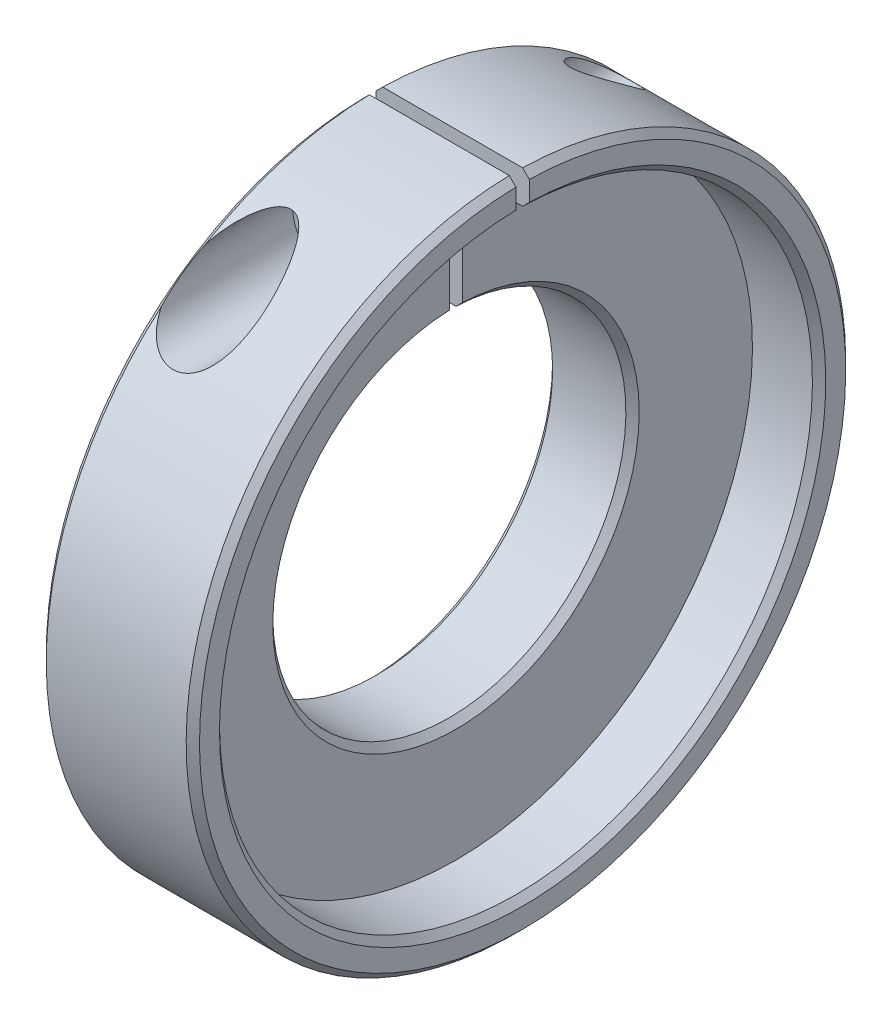
SolidWorks part; units mm, degrees
material "1.8901 (S460N)"
ref_plane "Plan de face" through (0, 0, 0) normal (0, 0, 1) x (1, 0, 0)
ref_plane "Plan de dessus" through (0, 0, 0) normal (0, 1, 0) x (1, 0, 0)
ref_plane "Plan de droite" through (0, 0, 0) normal (1, 0, 0) x (0, 0, -1)
sketch "Esquisse1" plane through (0, 0, 0) normal (0, 0, 1) x (1, 0, 0)
  line L0 (0, 0) -> (-25.4685, 0) construction
  line L1 (0, 13.25) -> (-6.5, 13.25)
  line L2 (-6.5, 13.25) -> (-6.5, 24.75)
  line L3 (-6.5, 24.75) -> (5, 24.75)
  line L4 (5, 24.75) -> (5, 22.25)
  line L5 (5, 22.25) -> (0, 22.25)
  line L6 (0, 22.25) -> (0, 13.25)
  dimension "D1" = 26.5
  dimension "D2" = 11.5
  dimension "D3" = 5
  dimension "D4" = 44.5
  dimension "D5" = 49.5
revolve "Révolution1" add sketch "Esquisse1" angle 360 about L0
sketch "Esquisse2" plane through (5, 0, 0) normal (1, 0, 0) x (0, 0, -1)
  line L1 (0.5, 0) -> (-0.5, 0)
  line L2 (0.5, 0) -> (0.5, 24.75)
  line L3 (0.5, 24.75) -> (-0.5, 24.75)
  line L4 (-0.5, 0) -> (-0.5, 24.75)
  circle A0 centre (0, 0) radius 24.75 construction
  dimension "D1" = 1
extrude "Enlèv. mat.-Extru.1" cut sketch "Esquisse2" against normal through all
sketch "Esquisse3" plane through (0, 0, 0) normal (0, 0, 1) x (1, 0, 0)
  line L0 (-3.25, 13.2406) -> (-3.25, 20) construction
  line L1 (0, 13.2406) -> (-6.5, 13.2406) construction
  circle A0 centre (-3.25, 20) radius 1.75
  dimension "D1" = 3.5
  dimension "D2" = 20
extrude "Enlèv. mat.-Extru.2" cut sketch "Esquisse3" against normal through all and the other way through all
ref_plane "Plan1" through (-3.25, 0, 0) normal (-1, 0, 0) x (0, 0, 1)
sketch "Esquisse4" plane through (-3.25, 0, 0) normal (-1, 0, 0) x (0, 0, 1)
  line L0 (6, 18.25) -> (6, 21.75) construction
  line L1 (6, 17) -> (17.9878, 17)
  line L2 (6, 17) -> (6, 20)
  line L3 (6, 20) -> (17.9878, 20)
  line L4 (17.9878, 17) -> (17.9878, 20)
  line L5 (0.5, 18.25) -> (16.7183, 18.25) construction
  line L6 (11.811, 21.75) -> (0.5, 21.75) construction
  line L7 (6, 20) -> (1.6627, 20) construction
  arc A0 (-0.5, 24.7449) -> (0.5, 24.7449) centre (0, 0) ccw construction
  dimension "D1" = 6
  dimension "D2" = 6
revolve "Enlèvement de matière-Révolution1" cut sketch "Esquisse4" angle 360 about L7
chamfer "Chanfrein1" distance 0.5 angle 45 5 edges at (5, -22.25, 0) (5, -24.75, 0) (-6.5, -24.75, 0) (0, -13.25, 0) (-6.5, -13.25, 0)
sketch "Esquisse5" plane through (0, 0, 0.5) normal (0, 0, -1) x (-1, 0, 0)
  circle A0 centre (3.25, 20) radius 2.05
  dimension "D1" = 4.1
extrude "Enlèv. mat.-Extru.3" cut sketch "Esquisse5" against normal through all
